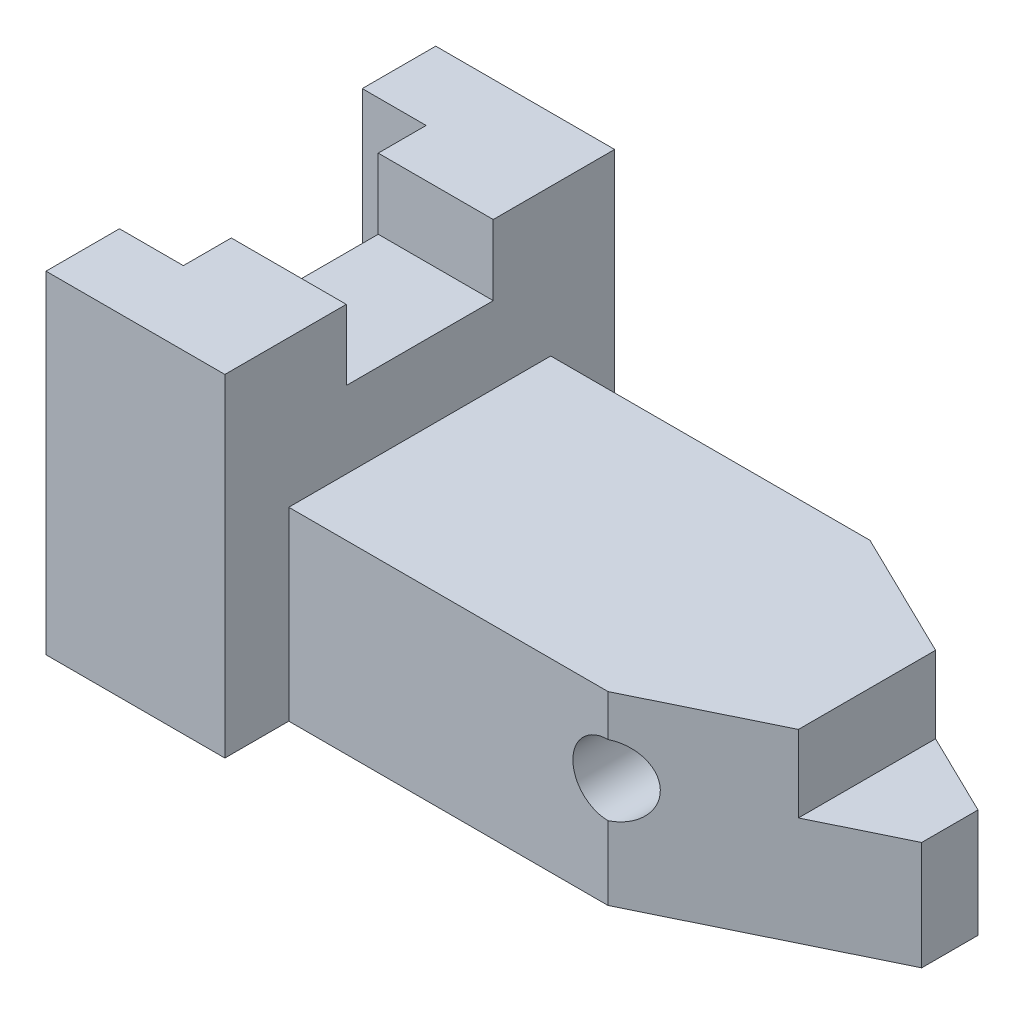
SolidWorks part; units mm, degrees
ref_plane "Front Plane" through (0, 0, 0) normal (0, 0, 1) x (1, 0, 0)
ref_plane "Top Plane" through (0, 0, 0) normal (0, 1, 0) x (1, 0, 0)
ref_plane "Right Plane" through (0, 0, 0) normal (1, 0, 0) x (0, 0, -1)
sketch "Sketch1" plane through (0, 0, 0) normal (0, 1, 0) x (1, 0, 0)
  line L0 (0, 0) -> (3584.2864, 0) construction
  line L1 (2818.6068, 111.8825) -> (2818.6068, 0)
  line L2 (2818.6068, 111.8825) -> (1980.4068, 520.7)
  line L3 (1980.4068, 520.7) -> (711.2, 520.7)
  line L4 (711.2, 520.7) -> (711.2, 774.7)
  line L5 (711.2, 774.7) -> (0, 774.7)
  line L6 (0, 774.7) -> (0, 482.6)
  line L7 (0, 482.6) -> (254, 482.6)
  line L8 (254, 482.6) -> (254, 292.1)
  line L11 (254, 292.1) -> (254, 0)
  line L12 (711.2, 520.7) -> (711.2, 0)
  line L13 (2818.6068, 111.8825) -> (3048, 0) construction
  line L15 (254, 0) -> (2818.6068, 0)
  point P20 (127, 482.6)
  dimension "D1" = 711.2
  dimension "D2" = 482.6
  dimension "D3" = 254
  dimension "D5" = 774.7
  dimension "D6" = 26
  dimension "D7" = 838.2
  dimension "D8" = 3048
  dimension "D9" = 520.7
extrude "Boss-Extrude1" add sketch "Sketch1" along normal blind 1320.8 contours L11 L15 L12 L4 L5 L6 L7 L8 region at (421.0127, 0, -429.1414)
extrude "Boss-Extrude2" add sketch "Sketch1<3>" along normal blind 736.6 contours L12 L15 L1 L2 L3 region at (1621.6347, 0, -237.392)
sketch "Sketch1<3>" plane through (0, 0, 0) normal (0, 1, 0) x (1, 0, 0) same geometry as "Sketch1"
mirror "Mirror2" about plane through (0, 1320.8, 0) normal (0, 0, -1) of "Boss-Extrude2", "Boss-Extrude1"
sketch "Sketch2" plane through (711.2, 0, 0) normal (1, 0, 0) x (0, 0, -1)
  line L0 (0, 0) -> (0, 1320.8) construction
  line L1 (111.8825, 0) -> (-111.8825, 0) construction
  line L2 (774.7, 1320.8) -> (-774.7, 1320.8) construction
  line L4 (-292.1, 1320.8) -> (292.1, 1320.8)
  line L5 (-292.1, 1320.8) -> (-292.1, 1041.4)
  line L6 (-292.1, 1041.4) -> (292.1, 1041.4)
  line L7 (292.1, 1320.8) -> (292.1, 1041.4)
  dimension "D1" = 584.2
  dimension "D2" = 279.4
extrude "Cut-Extrude1" cut sketch "Sketch2" against normal blind 736.6
sketch "Sketch3" plane through (0, 0, 520.7) normal (0, 0, 1) x (1, 0, 0)
  line L0 (2818.6068, 736.6) -> (1980.4068, 736.6) construction
  line L1 (2489.2, 1050.2561) -> (3234.7024, 1050.2561)
  line L2 (2489.2, 1050.2561) -> (2489.2, 431.8)
  line L3 (2489.2, 431.8) -> (3234.7024, 431.8)
  line L4 (3234.7024, 1050.2561) -> (3234.7024, 431.8)
  line L6 (0, 1320.8) -> (0, 0) construction
  dimension "D1" = 304.8
  dimension "D2" = 2489.2
extrude "Cut-Extrude2" cut sketch "Sketch3" against normal through all
sketch "Sketch4" plane through (0, 0, 520.7) normal (0, 0, 1) x (1, 0, 0)
  line L0 (1980.4068, 736.6) -> (1980.4068, 0) construction
  line L2 (2489.2, 431.8) -> (2818.6068, 431.8) construction
  circle A0 centre (1980.4068, 431.8) radius 139.7
  point P4 (0, 0)
  point P5 (0, 0)
  point P8 (0, 0)
  dimension "D1" = 279.4
extrude "Cut-Extrude3" cut sketch "Sketch4" against normal through all
